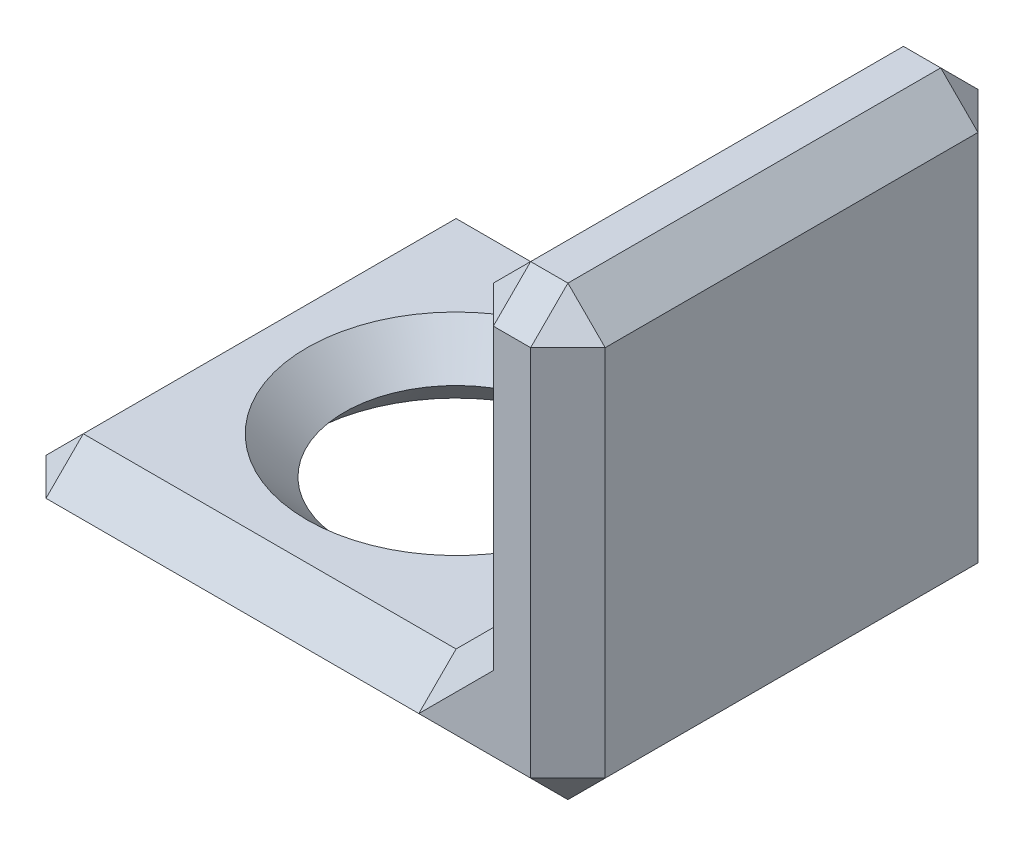
SolidWorks part; units mm, degrees
ref_plane "前视基准面" through (0, 0, 0) normal (0, 0, 1) x (1, 0, 0)
ref_plane "上视基准面" through (0, 0, 0) normal (0, 1, 0) x (1, 0, 0)
ref_plane "右视基准面" through (0, 0, 0) normal (1, 0, 0) x (0, 0, -1)
other "Configuration Table"
sketch "草图1" plane through (0, 0, 0) normal (0, 1, 0) x (1, 0, 0)
  line L1 (0, 0) -> (12, 0)
  line L2 (0, 0) -> (0, -12)
  line L3 (0, -12) -> (12, -12)
  line L4 (12, 0) -> (12, -12)
  circle A0 centre (6, -6) radius 3
  point P9 (-8.1945, -2.6114)
  dimension "D3" = 6
  dimension "D1" = 12
  dimension "D2" = 12
  dimension "D4" = 6
  dimension "D5" = 6
extrude "凸台-拉伸1" add sketch "草图1" along normal blind 2
sketch "草图2" plane through (0, 2, 0) normal (0, 1, 0) x (1, 0, 0)
  line L1 (12, 0) -> (15, 0)
  line L2 (12, 0) -> (12, -12)
  line L3 (12, -12) -> (15, -12)
  line L4 (15, 0) -> (15, -12)
  dimension "D1" = 3
extrude "凸台-拉伸2" add sketch "草图2" along normal blind 10 and the other way blind 2
chamfer "倒角1" distance 1 angle 45 18 edges at (6, 2, 9) (6, 0, 9) (0, 2, 6) (0, 0, 6) (12, 2, 6) (12, 12, 6) (13.5, 12, 0) (12, 7, 0) (6, 2, 0) (7.5, 0, 0) (15, 0, 6) (15, 6, 0) (15, 12, 6) (6, 2, 12) (12, 7, 12) (13.5, 12, 12) (15, 6, 12) (7.5, 0, 12)
